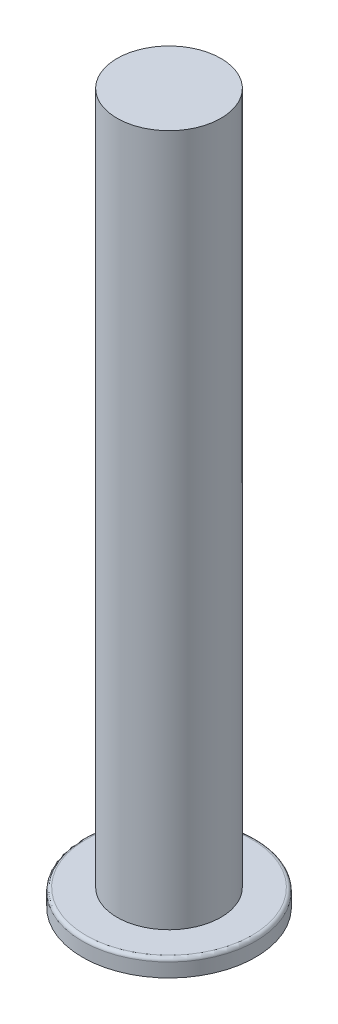
SolidWorks part; units mm, degrees
ref_plane "Front Plane" through (0, 0, 0) normal (0, 0, 1) x (1, 0, 0)
ref_plane "Top Plane" through (0, 0, 0) normal (0, 1, 0) x (1, 0, 0)
ref_plane "Right Plane" through (0, 0, 0) normal (1, 0, 0) x (0, 0, -1)
sketch "Sketch1" plane through (0, 0, 0) normal (0, 0, 1) x (1, 0, 0)
  line L0 (0, 0) -> (0, 200)
  line L1 (0, 200) -> (15, 200)
  line L2 (15, 200) -> (15, 0)
  line L4 (0, 0) -> (0, -5)
  line L9 (0, -5) -> (25, -5)
  line L10 (25, -5) -> (25, 0)
  line L11 (25, 0) -> (15, 0)
  dimension "D1" = 200
  dimension "D2" = 15
  dimension "D3" = 5
  dimension "D4" = 25
revolve "Revolve1" add sketch "Sketch1" angle 360 about L0
fillet "Fillet2" radius 1 1 edges at (0, 0, -25)
